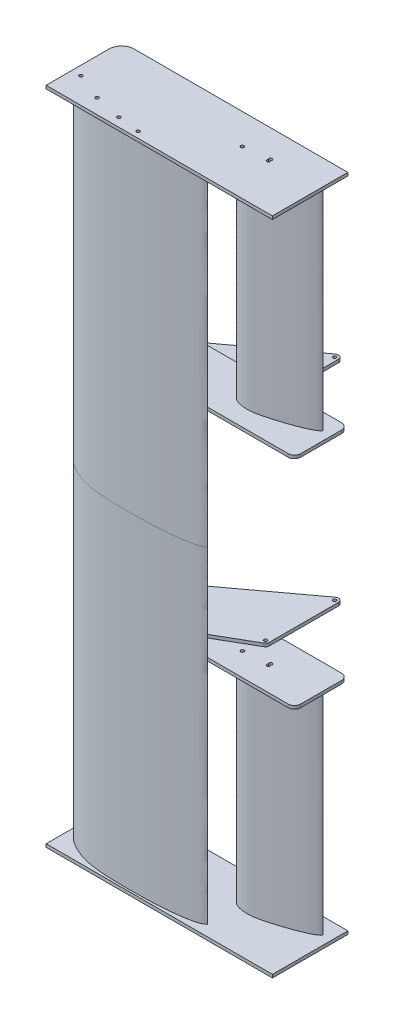
SolidWorks part; units mm, degrees
material "Pine"
ref_plane "Front Plane" through (0, 0, 0) normal (0, 0, 1) x (1, 0, 0)
ref_plane "Top Plane" through (0, 0, 0) normal (0, 1, 0) x (1, 0, 0)
ref_plane "Right Plane" through (0, 0, 0) normal (1, 0, 0) x (0, 0, -1)
curve "Curve1"
  spline degree 3 poles (-3.7953, 0, -0.0099) (-3.8135, 0, 0.0025) (-3.7975, 0, -0.0094) (-3.7869, 0, -0.0198) (-3.7634, 0, -0.0415) (-3.7356, 0, -0.0646) (-3.6977, 0, -0.0879) (-3.6505, 0, -0.1105) (-3.5935, 0, -0.134) (-3.5268, 0, -0.1582) (-3.4508, 0, -0.1829) (-3.3657, 0, -0.2079) (-3.2722, 0, -0.233) (-3.1706, 0, -0.258) (-3.0616, 0, -0.2828) (-2.9459, 0, -0.3071) (-2.8241, 0, -0.331) (-2.697, 0, -0.354) (-2.5653, 0, -0.3761) (-2.4298, 0, -0.3971) (-2.2915, 0, -0.417) (-2.1511, 0, -0.4356) (-2.0096, 0, -0.4529) (-1.8684, 0, -0.4689) (-1.7284, 0, -0.4834) (-1.5908, 0, -0.496) (-1.4567, 0, -0.506) (-1.3267, 0, -0.5129) (-1.2016, 0, -0.5159) (-1.082, 0, -0.5155) (-0.9682, 0, -0.5097) (-0.8601, 0, -0.4978) (-0.7573, 0, -0.4811) (-0.6597, 0, -0.4593) (-0.5675, 0, -0.4338) (-0.481, 0, -0.4051) (-0.4006, 0, -0.3736) (-0.3268, 0, -0.3398) (-0.2599, 0, -0.3041) (-0.2001, 0, -0.2671) (-0.148, 0, -0.2293) (-0.1034, 0, -0.1913) (-0.0671, 0, -0.1529) (-0.0392, 0, -0.1144) (-0.0186, 0, -0.0769) (-0.0054, 0, -0.0412) (0.0009, 0, -0.0084) (-0.0003, 0, 0.0194) (-0.0075, 0, 0.0449) (-0.0341, 0, 0.0576) (-0.0699, 0, 0.0593) (-0.1188, 0, 0.0611) (-0.1803, 0, 0.0584) (-0.2538, 0, 0.0535) (-0.3383, 0, 0.0457) (-0.433, 0, 0.0352) (-0.5376, 0, 0.0216) (-0.6518, 0, 0.0027) (-0.7763, 0, -0.0211) (-0.9117, 0, -0.0469) (-1.0573, 0, -0.0742) (-1.2123, 0, -0.1018) (-1.3754, 0, -0.1287) (-1.5454, 0, -0.154) (-1.7209, 0, -0.1767) (-1.9002, 0, -0.1962) (-2.0817, 0, -0.2116) (-2.2636, 0, -0.2225) (-2.4439, 0, -0.2285) (-2.6207, 0, -0.2293) (-2.792, 0, -0.2247) (-2.9559, 0, -0.215) (-3.1104, 0, -0.2002) (-3.2537, 0, -0.1809) (-3.3838, 0, -0.1577) (-3.4993, 0, -0.1313) (-3.598, 0, -0.103) (-3.6788, 0, -0.0729) (-3.7364, 0, -0.0453) (-3.7789, 0, -0.0198) (-3.7953, 0, -0.0099) (-3.8135, 0, 0.0025) (-3.7975, 0, -0.0094) knots -0.009748 -0.004147 -0.001 0 0.00098 0.003649 0.007483 0.012095 0.017526 0.024052 0.031783 0.040678 0.05071 0.061833 0.073989 0.087118 0.101145 0.115991 0.13157 0.147788 0.164551 0.181758 0.199312 0.217095 0.23499 0.252857 0.270541 0.287887 0.304773 0.321101 0.336806 0.3518 0.366031 0.379616 0.392653 0.40517 0.417172 0.428604 0.439419 0.449597 0.459102 0.467908 0.475988 0.483309 0.489875 0.495803 0.501149 0.505903 0.510047 0.513579 0.516447 0.51935 0.523823 0.529974 0.537716 0.546968 0.557637 0.56962 0.582804 0.597247 0.613135 0.630444 0.649056 0.668822 0.689595 0.71119 0.733427 0.756094 0.778989 0.80189 0.824567 0.846792 0.868338 0.888978 0.908492 0.926659 0.943286 0.958169 0.971136 0.981956 0.990252 0.995853 0.999 1 1.00098 1.003649 1.007483 periodic
sketch "Sketch1" plane through (0, 0, 0) normal (0, 1, 0) x (1, 0, 0)
  line L0 (318.0838, 47.2592) -> (20.32, 83.82) construction
  line L1 (9.5805, -3.6465) -> (6065.9065, 49321.1705) construction
  line L2 (-1177.287, 83.82) -> (48822.713, 83.82) construction
  spline S1 degree 3 poles (317.0165, 46.6419) (318.3773, 47.4184) (316.8369, 46.627) (315.4664, 46.0116) (311.9008, 44.4244) (307.1317, 42.8195) (300.5288, 41.2362) (292.543, 39.973) (283.2645, 39.0147) (272.8721, 38.4436) (261.4925, 38.3058) (249.2768, 38.6273) (236.3743, 39.4349) (222.9401, 40.7195) (209.1286, 42.4707) (195.0934, 44.6655) (180.9844, 47.2597) (166.9459, 50.2011) (153.1164, 53.4411) (139.6198, 56.8949) (126.5733, 60.4959) (114.0825, 64.1576) (102.2376, 67.7976) (91.1177, 71.3243) (80.7835, 74.6402) (71.2804, 77.6879) (62.5337, 80.2614) (54.4946, 82.3207) (47.1899, 84.0534) (40.658, 85.4728) (34.9649, 86.5566) (30.181, 87.3528) (26.3404, 87.6865) (23.5279, 87.89) (21.3276, 87.1554) (20.5243, 85.2313) (20.1634, 83.0703) (20.3406, 80.4413) (21.0319, 77.5319) (22.2833, 74.4034) (24.0944, 71.1235) (26.5649, 67.7742) (29.6846, 64.3831) (33.3989, 60.9242) (37.7138, 57.4603) (42.6049, 54.0342) (48.0476, 50.6811) (54.0299, 47.457) (60.5145, 44.3798) (67.479, 41.5056) (74.8973, 38.8735) (82.773, 36.5786) (91.1076, 34.6171) (99.9461, 33.0706) (109.2874, 31.9018) (119.0924, 30.9371) (129.3172, 30.2311) (139.8976, 29.7294) (150.7687, 29.3974) (161.8479, 29.189) (173.0437, 29.0939) (184.2607, 29.0916) (195.4117, 29.2025) (206.4168, 29.4317) (217.205, 29.7753) (227.7083, 30.245) (237.8646, 30.8257) (247.6112, 31.5224) (256.8894, 32.3192) (265.643, 33.213) (273.8196, 34.1979) (281.3721, 35.2653) (288.2578, 36.4021) (294.4384, 37.6037) (299.881, 38.8572) (304.5597, 40.1522) (308.4644, 41.4638) (311.6537, 42.9201) (314.0433, 44.4595) (316.0892, 45.931) (317.0165, 46.6419) (318.3773, 47.4184) (316.8369, 46.627) knots -0.007483 -0.003649 -0.00098 0 0.001 0.004147 0.009748 0.018044 0.028864 0.041831 0.056714 0.073341 0.091508 0.111022 0.131662 0.153208 0.175433 0.19811 0.221011 0.243906 0.266573 0.28881 0.310405 0.331178 0.350944 0.369556 0.386865 0.402753 0.417196 0.43038 0.442363 0.453032 0.462284 0.470026 0.476177 0.48065 0.483553 0.486421 0.489953 0.494097 0.498851 0.504197 0.510125 0.516691 0.524012 0.532092 0.540898 0.550403 0.560581 0.571396 0.582828 0.59483 0.607347 0.620384 0.633969 0.6482 0.663194 0.678899 0.695227 0.712113 0.729459 0.747143 0.76501 0.782905 0.800688 0.818242 0.835449 0.852212 0.86843 0.884009 0.898855 0.912882 0.926011 0.938167 0.94929 0.959322 0.968217 0.975948 0.982474 0.987905 0.992517 0.996351 0.99902 1 1.001 1.004147 1.009748 only from (318.0838, 47.2592) to (318.0838, 47.2592)
  dimension "D1" = 7
  dimension "D2" = 300
  dimension "D3" = 83.82
  dimension "D4" = 20.32
extrude "Main" add sketch "Sketch1" along normal blind 660.4
sketch "Sketch2" plane through (0, 660.4, 0) normal (0, 1, 0) x (1, 0, 0)
  line L1 (13.97, 25.4) -> (471.17, 25.4)
  line L2 (13.97, 25.4) -> (13.97, 177.8)
  line L3 (13.97, 177.8) -> (471.17, 177.8)
  line L4 (471.17, 25.4) -> (471.17, 177.8)
  line L5 (13.97, 25.4) -> (471.17, 177.8) construction
  line L6 (13.97, 177.8) -> (471.17, 25.4) construction
  point P4 (242.57, 101.6)
  dimension "D1" = 152.4
  dimension "D2" = 457.2
  dimension "D3" = 25.4
  dimension "D4" = 13.97
extrude "Endplate" add sketch "Sketch2" along normal blind 6.35 separate body
fillet "Fillet4" radius 25.4 1 edges at (13.97, 663.575, -177.8)
sketch "Sketch3" plane through (0, 660.4, 0) normal (0, 1, 0) x (1, 0, 0)
  line L0 (453.7912, 145.4272) -> (306.07, 119.38) construction
  line L1 (293.3107, 191.7414) -> (-6897.794, 40974.5231) construction
  line L2 (-1185.6674, 119.38) -> (48814.3326, 119.38) construction
  line L5 (13.97, 25.4) -> (471.17, 25.4) construction
  line L6 (13.97, 152.4) -> (13.97, 25.4) construction
  spline S1 degree 3 poles (453.3711, 144.976) (453.9082, 145.5462) (453.2873, 144.9427) (452.722, 144.4481) (451.2491, 143.1679) (449.2034, 141.7033) (446.2777, 139.981) (442.6439, 138.2096) (438.3474, 136.395) (433.4618, 134.6027) (428.0407, 132.8733) (422.1528, 131.2412) (415.8653, 129.7412) (409.2539, 128.3916) (402.3939, 127.2099) (395.3622, 126.2076) (388.2367, 125.3855) (381.0941, 124.7397) (374.0079, 124.2672) (367.0496, 123.9457) (360.2849, 123.7603) (353.7771, 123.6851) (347.5813, 123.6941) (341.7488, 123.7548) (336.3227, 123.8296) (331.3332, 123.8976) (326.7748, 123.8495) (322.6298, 123.659) (318.8838, 123.4196) (315.5531, 123.1434) (312.6724, 122.8294) (310.2686, 122.5108) (308.3834, 122.1089) (307.0089, 121.795) (306.0642, 121.1222) (305.9614, 120.0847) (306.1047, 118.9986) (306.5738, 117.7675) (307.3296, 116.4774) (308.3853, 115.1645) (309.7308, 113.8609) (311.4017, 112.6206) (313.3891, 111.4552) (315.6707, 110.3443) (318.2403, 109.3188) (321.0798, 108.3956) (324.1724, 107.5879) (327.5042, 106.9209) (331.0547, 106.3974) (334.805, 106.0413) (338.7368, 105.8672) (342.8381, 105.9212) (347.11, 106.2017) (351.5623, 106.7543) (356.1997, 107.561) (361.029, 108.533) (366.0212, 109.6902) (371.1536, 110.997) (376.4001, 112.4275) (381.7282, 113.9474) (387.0954, 115.5386) (392.4592, 117.1773) (397.7748, 118.8605) (403.0034, 120.5788) (408.1116, 122.3202) (413.0651, 124.0802) (417.8365, 125.8426) (422.395, 127.6006) (426.7149, 129.3379) (430.7698, 131.0449) (434.5355, 132.7111) (437.9907, 134.3256) (441.1169, 135.8757) (443.8965, 137.3538) (446.3157, 138.7488) (448.3635, 140.0519) (450.0388, 141.2499) (451.3509, 142.4125) (452.2684, 143.4979) (453.0316, 144.5006) (453.3711, 144.976) (453.9082, 145.5462) (453.2873, 144.9427) knots -0.007483 -0.003649 -0.00098 0 0.001 0.004147 0.009748 0.018044 0.028864 0.041831 0.056714 0.073341 0.091508 0.111022 0.131662 0.153208 0.175433 0.19811 0.221011 0.243906 0.266573 0.28881 0.310405 0.331178 0.350944 0.369556 0.386865 0.402753 0.417196 0.43038 0.442363 0.453032 0.462284 0.470026 0.476177 0.48065 0.483553 0.486421 0.489953 0.494097 0.498851 0.504197 0.510125 0.516691 0.524012 0.532092 0.540898 0.550403 0.560581 0.571396 0.582828 0.59483 0.607347 0.620384 0.633969 0.6482 0.663194 0.678899 0.695227 0.712113 0.729459 0.747143 0.76501 0.782905 0.800688 0.818242 0.835449 0.852212 0.86843 0.884009 0.898855 0.912882 0.926011 0.938167 0.94929 0.959322 0.968217 0.975948 0.982474 0.987905 0.992517 0.996351 0.99902 1 1.001 1.004147 1.009748 only from (453.7912, 145.4272) to (453.7912, 145.4272)
  dimension "D1" = 150
  dimension "D2" = 10
  dimension "D3" = 93.98
  dimension "D4" = 292.1
extrude "Second" add sketch "Sketch3" against normal blind 438.15 separate body
sketch "Reference Sketch" plane through (0, 222.25, 0) normal (0, -1, 0) x (1, 0, 0)
  line L8 (318.0838, -47.2592) -> (20.32, -83.82) construction
  line L9 (318.0838, -47.2592) -> (20.32, -83.82) construction
  line L10 (58.136, -79.1768) -> (59.6837, -91.7821) construction
  line L11 (171.584, -65.2471) -> (170.9649, -60.205) construction
  line L14 (453.7912, -145.4272) -> (306.07, -119.38) construction
  line L15 (453.7912, -145.4272) -> (306.07, -119.38) construction
  line L17 (319.4592, -116.5825) -> (318.5771, -121.5853) construction
  line L18 (32.3062, -77.2301) -> (32.9253, -82.2723) construction
  line L19 (370.8106, -117.8996) -> (368.6053, -130.4067) construction
  line L29 (330.2, -292.1) -> (330.2, -152.4) construction
  line L30 (87.173, -55.1389) -> (89.6493, -75.3074) construction
  line L31 (143.2779, -43.1319) -> (146.3734, -68.3426) construction
  line L32 (187.3966, -37.7148) -> (190.492, -62.9255) construction
  circle A0 centre (170.9649, -60.205) radius 3.302
  circle A1 centre (59.6837, -91.7821) radius 3.302
  circle A2 centre (59.6837, -91.7821) radius 7.62 construction
  circle A3 centre (170.9649, -60.205) radius 7.62 construction
  circle A7 centre (319.4592, -116.5825) radius 3.302 construction
  circle A9 centre (370.8106, -117.8996) radius 3.302 construction
  circle A10 centre (330.2, -292.1) radius 3.302
  circle A11 centre (330.2, -152.4) radius 3.302
  circle A12 centre (330.2, -292.1) radius 7.62 construction
  circle A13 centre (330.2, -152.4) radius 7.62 construction
  circle A14 centre (32.3062, -77.2301) radius 3.302 construction
  circle A15 centre (87.173, -55.1389) radius 3.302 construction
  circle A16 centre (143.2779, -43.1319) radius 3.302 construction
  circle A17 centre (187.3966, -37.7148) radius 3.302
  dimension "D5" = 6.604
  dimension "D6" = 15.24
  dimension "D7" = 6.604
  dimension "D14" = 6.604
  dimension "D15" = 69.85
  dimension "D1" = 38.1
  dimension "D2" = 12.7
  dimension "D3" = 152.4
  dimension "D4" = 5.08
  dimension "D8" = 5.08
  dimension "D9" = 12.7
  dimension "D10" = 12.7
  dimension "D11" = 12.7
  dimension "D12" = 5.08
  dimension "D13" = 63.5
  dimension "D16" = 139.7
  dimension "D17" = 330.2
  dimension "D18" = 152.4
  dimension "D19" = 20.32
  dimension "D20" = 25.4
  dimension "D21" = 127
  dimension "D22" = 171.45
  dimension "D23" = 25.4
sketch "Sketch23" plane through (0, 222.25, 0) normal (0, -1, 0) x (1, 0, 0)
  line L1 (57.6036, -84.4515) -> (168.8848, -52.8744)
  line L3 (471.17, -177.8) -> (471.17, -69.85)
  line L6 (55.1491, -97.9059) -> (163.0408, -177.8)
  line L7 (471.17, -177.8) -> (39.37, -177.8) construction
  line L8 (163.0408, -177.8) -> (471.17, -177.8)
  line L9 (174.783, -53.6105) -> (202.8311, -69.85)
  line L10 (202.8311, -69.85) -> (471.17, -69.85)
  line L11 (174.783, -53.6105) -> (334.0181, -145.8056) construction
  line L12 (325.6653, -298.2238) -> (55.1491, -97.9059) construction
  line L13 (471.17, -25.4) -> (471.17, -177.8) construction
  circle A0 centre (59.6837, -91.7821) radius 7.62 construction
  circle A1 centre (330.2, -152.4) radius 7.62 construction
  circle A2 centre (170.9649, -60.205) radius 7.62 construction
  circle A3 centre (59.6837, -91.7821) radius 7.62 construction
  circle A6 centre (330.2, -152.4) radius 3.302 construction
  circle A7 centre (330.2, -152.4) radius 3.302
  circle A8 centre (59.6837, -91.7821) radius 3.302 construction
  circle A9 centre (59.6837, -91.7821) radius 3.302
  circle A10 centre (170.9649, -60.205) radius 3.302 construction
  circle A11 centre (170.9649, -60.205) radius 3.302
  arc A12 (174.783, -53.6105) -> (168.8848, -52.8744) centre (170.9649, -60.205) ccw
  arc A13 (55.1491, -97.9059) -> (57.6036, -84.4515) centre (59.6837, -91.7821) cw
  circle A15 centre (330.2, -292.1) radius 7.62 construction
  dimension "D1" = 107.95
extrude "Inner Endplate" add sketch "Sketch23" along normal blind 6.35 separate body
fillet "Fillet2" radius 12.7 4 edges at (202.8311, 219.075, -69.85) (471.17, 219.075, -69.85) (471.17, 219.075, -177.8) (163.0408, 219.075, -177.8)
sketch "Sketch24" plane through (0, 215.9, 0) normal (0, -1, 0) x (1, 0, 0)
  line L0 (305.8771, -118.2024) -> (450.766, -157.0253) construction
  line L1 (319.4592, -116.5825) -> (318.1444, -121.4894) construction
  line L5 (-713.9399, -118.2024) -> (49286.0601, -118.2024) construction
  line L6 (370.5004, -122.3702) -> (367.2134, -134.6374) construction
  line L7 (319.4592, -116.5825) -> (318.5771, -121.5853) construction
  line L8 (370.8106, -117.8996) -> (368.6053, -130.4067) construction
  line L9 (453.7912, -145.4272) -> (306.07, -119.38) construction
  arc A0 (368.2359, -119.967) -> (373.0751, -120.3028) centre (370.5004, -122.3702) ccw
  circle A2 centre (319.4592, -116.5825) radius 3.302 construction
  circle A3 centre (370.8106, -117.8996) radius 3.302 construction
  circle A4 centre (319.4592, -116.5825) radius 3.302
  arc A5 (373.0751, -120.3028) -> (368.2359, -119.967) centre (370.8106, -117.8996) ccw
  circle A6 centre (143.2779, -43.1319) radius 3.302 construction
  circle A7 centre (87.173, -55.1389) radius 3.302 construction
  circle A8 centre (32.3062, -77.2301) radius 3.302 construction
  circle A9 centre (143.2779, -43.1319) radius 3.302
  circle A10 centre (87.173, -55.1389) radius 3.302
  circle A11 centre (32.3062, -77.2301) radius 3.302
  circle A12 centre (187.3966, -37.7148) radius 3.302 construction
  circle A13 centre (187.3966, -37.7148) radius 3.302
  dimension "D1" = 15
  dimension "D2" = 12.7
  dimension "D3" = 63.5
extrude "Cut-Extrude4" cut sketch "Sketch24" against normal through all both and the other way through all
ref_plane "Plane1" through (0, 215.9, 0) normal (0, -1, 0) x (-1, 0, 0)
mirror "Mirror1" about plane through (21.2959, 0, -76.9872) normal (0, -1, 0) of bodies 143 103 101 144 105 126 134
sketch "Sketch8" plane through (0, 215.9, 0) normal (0, -1, 0) x (1, 0, 0)
  line L0 (55.1491, -97.9059) -> (325.6653, -298.2238)
  line L3 (337.82, -292.1) -> (337.82, -152.4)
  line L6 (174.783, -53.6105) -> (334.0181, -145.8056)
  line L9 (168.8848, -52.8744) -> (57.6036, -84.4515)
  circle A7 centre (170.9649, -60.205) radius 7.62 construction
  circle A22 centre (59.6837, -91.7821) radius 7.62 construction
  circle A23 centre (330.2, -152.4) radius 7.62 construction
  circle A24 centre (330.2, -292.1) radius 7.62 construction
  arc A26 (325.6653, -298.2238) -> (337.82, -292.1) centre (330.2, -292.1) ccw
  arc A27 (334.0181, -145.8056) -> (337.82, -152.4) centre (330.2, -152.4) cw
  arc A28 (57.6036, -84.4515) -> (55.1491, -97.9059) centre (59.6837, -91.7821) ccw
  arc A29 (168.8848, -52.8744) -> (174.783, -53.6105) centre (170.9649, -60.205) cw
  circle A30 centre (170.9649, -60.205) radius 7.62 construction
extrude "Bracket" add sketch "Sketch8" along normal blind 6.35 separate body
sketch "Sketch9" plane through (0, 215.9, 0) normal (0, -1, 0) x (1, 0, 0)
  circle A0 centre (59.6837, -91.7821) radius 3.302
  circle A1 centre (170.9649, -60.205) radius 3.302
  circle A2 centre (330.2, -152.4) radius 3.302
  circle A3 centre (330.2, -292.1) radius 3.302
  circle A8 centre (330.2, -152.4) radius 7.62 construction
  circle A9 centre (330.2, -292.1) radius 7.62 construction
  circle A10 centre (59.6837, -91.7821) radius 7.62 construction
  circle A11 centre (170.9649, -60.205) radius 7.62 construction
  dimension "D1" = 6.604
extrude "Cut-Extrude1" cut sketch "Sketch9" against normal through all both and the other way through all
mirror "Mirror2" about plane through (0, 0, 0) normal (0, 1, 0) of bodies 122
ref_axis "Axis1" through (13.97, 660.4, -25.4) along (0, -1, 0)
